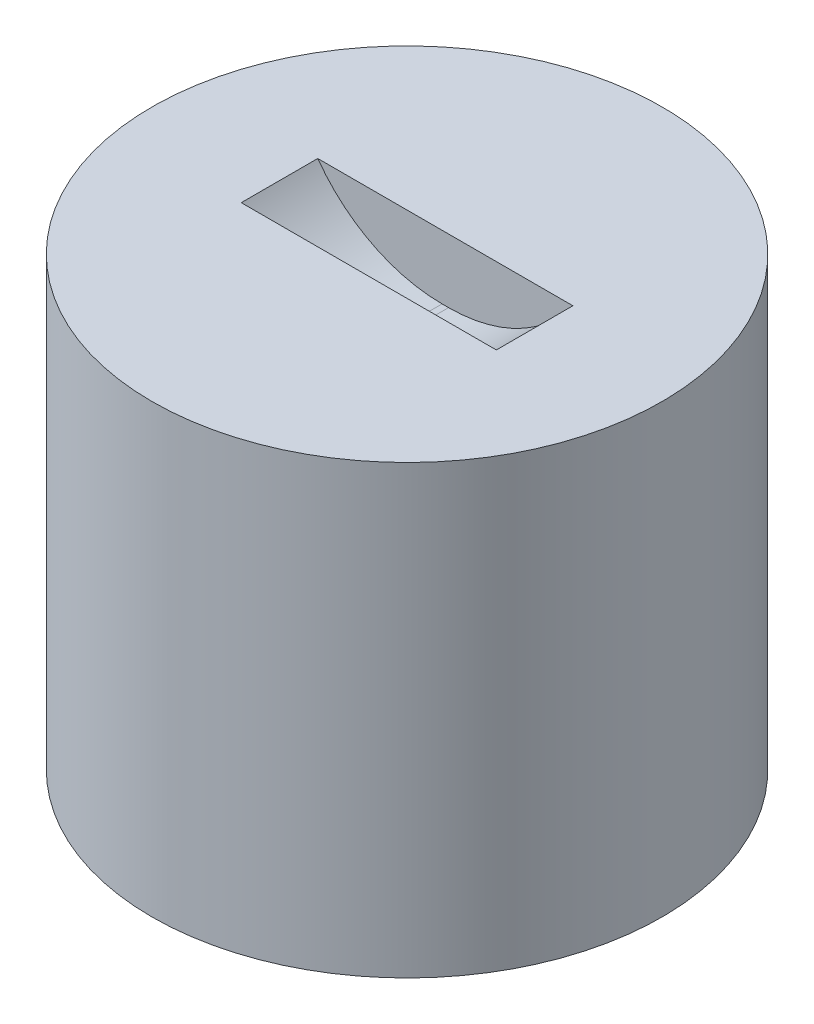
SolidWorks part; units mm, degrees
ref_plane "Front Plane" through (0, 0, 0) normal (0, 0, 1) x (1, 0, 0)
ref_plane "Top Plane" through (0, 0, 0) normal (0, 1, 0) x (1, 0, 0)
ref_plane "Right Plane" through (0, 0, 0) normal (1, 0, 0) x (0, 0, -1)
sketch "Sketch1" plane through (0, 0, 0) normal (0, 1, 0) x (1, 0, 0)
  circle A0 centre (0, 0) radius 20
  dimension "D1" = 40
extrude "Boss-Extrude1" add sketch "Sketch1" along normal blind 35
sketch "Sketch2" plane through (0, 35, 0) normal (0, 1, 0) x (1, 0, 0)
  line L1 (10, 3) -> (-10, 3)
  line L2 (10, 3) -> (10, -3)
  line L3 (10, -3) -> (-10, -3)
  line L4 (-10, 3) -> (-10, -3)
  line L5 (10, 3) -> (-10, -3) construction
  line L6 (10, -3) -> (-10, 3) construction
  point P0 (0, 0)
  dimension "D1" = 6
  dimension "D2" = 20
extrude "Cut-Extrude1" cut sketch "Sketch2" against normal blind 5
fillet "Fillet1" radius 12 2 edges at (10, 30, 0) (-10, 30, 0)
